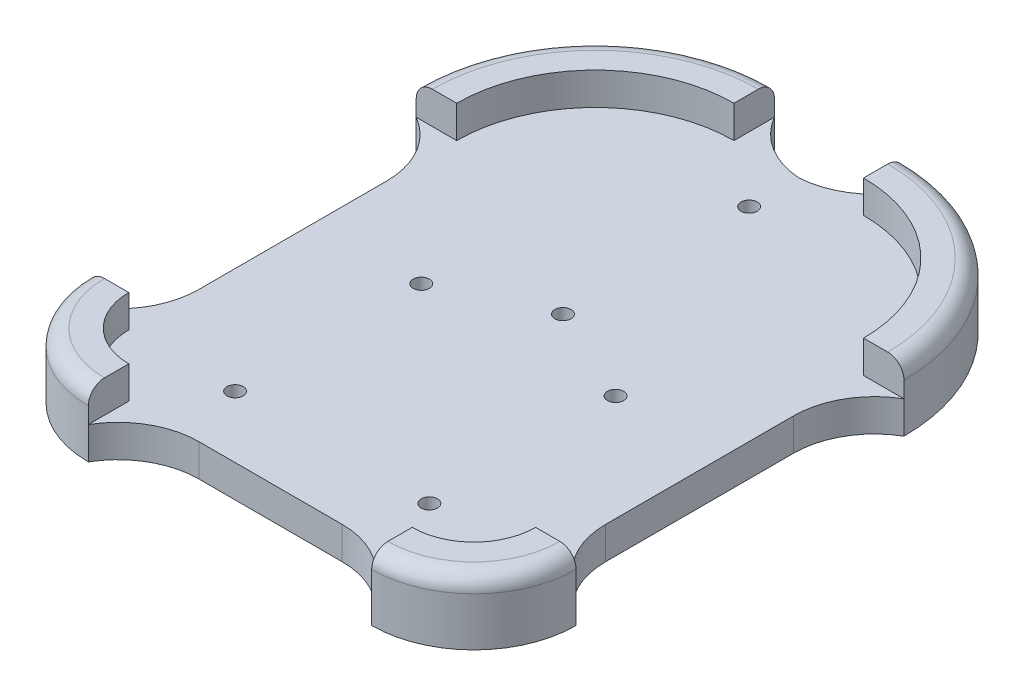
SolidWorks part; units mm, degrees
note: The reader was unsure of these and kept them because the rebuilt part matched: shared geometry of "Croquis1<3>", "Croquis3<3>".
ref_plane "Alzado" through (0, 0, 0) normal (0, 0, 1) x (1, 0, 0)
ref_plane "Planta" through (0, 0, 0) normal (0, 1, 0) x (1, 0, 0)
ref_plane "Vista lateral" through (0, 0, 0) normal (1, 0, 0) x (0, 0, -1)
sketch "Croquis1" plane through (0, 0, 0) normal (0, 1, 0) x (1, 0, 0)
  line L0 (17.5, 0) -> (-17.5, 0) construction
  line L1 (25, 7.5) -> (25, 48) construction
  line L2 (8, 65) -> (-8, 65) construction
  line L3 (0, -41.3875) -> (0, 41.3875) construction
  line L4 (-25, 7.5) -> (-25, 48) construction
  line L5 (17.5, -0.125) -> (-17.5, -0.125)
  line L6 (-25.125, 7.5) -> (-25.125, 48)
  line L7 (8, 65.125) -> (-8, 65.125)
  line L8 (25.125, 7.5) -> (25.125, 48)
  line L9 (-8, 70.125) -> (-8, 65.125)
  line L10 (-30.125, 48) -> (-25, 48)
  line L11 (-30.125, 7.5) -> (-25.125, 7.5)
  line L12 (-17.5, 0) -> (-17.5, -5.125)
  line L13 (17.5, -5.125) -> (17.5, -0.125)
  line L14 (25, 7.5) -> (30.125, 7.5)
  line L15 (8, 70.125) -> (8, 65.125)
  line L16 (30.125, 48) -> (25, 48)
  arc A0 (25, 48) -> (8, 65) centre (8, 48) ccw construction
  arc A1 (17.5, 0) -> (25, 7.5) centre (17.5, 7.5) ccw construction
  arc A2 (-17.5, 0) -> (-25, 7.5) centre (-17.5, 7.5) cw construction
  arc A3 (-25, 48) -> (-8, 65) centre (-8, 48) cw construction
  arc A4 (-17.5, -0.125) -> (-25.125, 7.5) centre (-17.5, 7.5) cw
  arc A5 (-25.125, 48) -> (-8, 65.125) centre (-8, 48) cw
  arc A6 (25.125, 48) -> (8, 65.125) centre (8, 48) ccw
  arc A7 (17.5, -0.125) -> (25.125, 7.5) centre (17.5, 7.5) ccw
  arc A8 (30.125, 48) -> (8, 70.125) centre (8, 48) ccw
  arc A9 (17.5, -5.125) -> (30.125, 7.5) centre (17.5, 7.5) ccw
  arc A10 (-30.125, 48) -> (-8, 70.125) centre (-8, 48) cw
  arc A11 (-17.5, -5.125) -> (-30.125, 7.5) centre (-17.5, 7.5) cw
  point P7 (0, 0)
  point P18 (0, 65)
  dimension "D2" = 17
  dimension "D4" = 7.5
  dimension "D1" = 8
  dimension "D3" = 40.5
  dimension "D5" = 0.125
  dimension "D6" = 5
  dimension "D7" = 5
extrude "Saliente-Extruir1" add sketch "Croquis1" along normal blind 4
extrude "Saliente-Extruir2" add sketch "Croquis1<3>" along normal blind 4 from surface at 4 contours A10 L10 A5 L9 | A11 L12 A4 L11 | L13 A9 L14 A7 | L16 A8 L15 A6 starting at face at (0, 4, -30.3709)
sketch "Croquis1<3>" plane through (0, 0, 0) normal (0, 1, 0) x (1, 0, 0) same geometry as "Croquis1"
fillet "Redondeo1" radius 10 8 edges at (8, 2, -65.125) (-8, 2, -65.125) (-17.5, 2, 0.125) (17.5, 2, 0.125) (25.125, 2, -48) (25.125, 2, -7.5) (-25.125, 2, -7.5) (-25.125, 2, -48)
fillet "Redondeo3" radius 2 4 edges at (26.4272, 8, 1.4272) (23.6447, 8, -63.6447) (-23.6447, 8, -63.6447) (-26.4272, 8, 1.4272)
sketch "Croquis3" plane through (0, 0, 0) normal (0, 1, 0) x (1, 0, 0)
  line L0 (-9.5, 10.3542) -> (-9.5, 6.1542)
  line L1 (-9.5, 27.6458) -> (-9.5, 31.8458)
  line L2 (-11.7, 34.0458) -> (-12.3, 34.0458)
  line L3 (-14.5, 27.6458) -> (-14.5, 31.8458)
  line L4 (-11.7, 3.9542) -> (-12.3, 3.9542)
  line L5 (-14.5, 10.3542) -> (-14.5, 6.1542)
  line L6 (0, -4.4) -> (0, 4.4) construction
  line L7 (14.5, 10.3542) -> (14.5, 6.1542)
  line L8 (11.7, 3.9542) -> (12.3, 3.9542)
  line L9 (14.5, 27.6458) -> (14.5, 31.8458)
  line L10 (11.7, 34.0458) -> (12.3, 34.0458)
  line L11 (9.5, 27.6458) -> (9.5, 31.8458)
  line L12 (9.5, 10.3542) -> (9.5, 6.1542)
  line L13 (2.5, 56.1458) -> (2.5, 60.3458)
  line L14 (2.5, 38.8542) -> (2.5, 34.6542)
  line L15 (0.3, 32.4542) -> (-0.3, 32.4542)
  line L22 (0.3, 62.5458) -> (-0.3, 62.5458)
  line L23 (-2.5, 56.1458) -> (-2.5, 60.3458)
  line L27 (-2.5, 38.8542) -> (-2.5, 34.6542)
  arc A0 (9.5, 10.3542) -> (9.5, 27.6458) centre (12, 19) cw
  arc A1 (-14.5, 27.6458) -> (-14.5, 10.3542) centre (-12, 19) ccw
  circle A2 centre (-12, 30.5) radius 1
  arc A3 (-9.5, 31.8458) -> (-11.7, 34.0458) centre (-11.7, 31.8458) ccw
  arc A4 (-12.3, 34.0458) -> (-14.5, 31.8458) centre (-12.3, 31.8458) ccw
  arc A5 (12.3, 3.9542) -> (14.5, 6.1542) centre (12.3, 6.1542) ccw
  circle A6 centre (-12, 7.5) radius 1
  arc A7 (-9.5, 6.1542) -> (-11.7, 3.9542) centre (-11.7, 6.1542) cw
  arc A8 (-12.3, 3.9542) -> (-14.5, 6.1542) centre (-12.3, 6.1542) cw
  arc A9 (-9.5, 10.3542) -> (-9.5, 27.6458) centre (-12, 19) ccw
  arc A10 (9.5, 6.1542) -> (11.7, 3.9542) centre (11.7, 6.1542) ccw
  circle A11 centre (12, 7.5) radius 1
  arc A12 (12.3, 34.0458) -> (14.5, 31.8458) centre (12.3, 31.8458) cw
  arc A13 (9.5, 31.8458) -> (11.7, 34.0458) centre (11.7, 31.8458) cw
  circle A14 centre (12, 30.5) radius 1
  arc A15 (14.5, 27.6458) -> (14.5, 10.3542) centre (12, 19) cw
  circle A24 centre (0, 47.5) radius 9
  circle A25 centre (0, 59) radius 1
  arc A26 (2.5, 60.3458) -> (0.3, 62.5458) centre (0.3, 60.3458) ccw
  arc A27 (-0.3, 62.5458) -> (-2.5, 60.3458) centre (-0.3, 60.3458) ccw
  circle A31 centre (0, 36) radius 1
  arc A32 (2.5, 34.6542) -> (0.3, 32.4542) centre (0.3, 34.6542) cw
  arc A33 (-0.3, 32.4542) -> (-2.5, 34.6542) centre (-0.3, 34.6542) cw
  point P1 (-12, 3.9542)
  point P14 (-12, 34.0458)
  point P51 (0, 62.5458)
  point P60 (-0.7004, 60.4859)
  point P61 (0, 0)
  point P62 (0, 0)
  point P63 (0, 0)
  point P64 (0, 0)
  point P65 (0, 0)
  point P66 (0, 0)
  point P67 (0, 0)
  point P68 (0, 37.2261)
  point P73 (0, 0)
  point P76 (0, 0)
  point P77 (0, 0)
  point P78 (0, 0)
  point P79 (0, 32.4542)
  dimension "D3" = 2
  dimension "D4" = 2.2
  dimension "D6" = 9
  dimension "D12" = 2.2
  dimension "D1" = 5
  dimension "D2" = 11.5
  dimension "D5" = 11.5
  dimension "D7" = 6.4
  dimension "D8" = 12
  dimension "D9" = 19
  dimension "D10" = 5
  dimension "D11" = 11.5
  dimension "D13" = 6.4
  dimension "D14" = 47.5
  dimension "D15" = 11.5
extrude "Cortar-Extruir1" cut sketch "Croquis3" along normal blind 2 contours A9 L0 A7 L4 A8 L5 A1 L3 A4 L2 A3 L1 A6 A2 | L9 A15 L7 A5 L8 A10 L12 A0 L11 A13 L10 A12 A11 A14 | A24 | L15 A33 L27 A24 L14 A32 A31 | A27 L22 A26 L13 A24 L23 A25
extrude "Cortar-Extruir2" cut sketch "Croquis3<3>" along normal through all contours A6 | A2 | A11 | A14 | A25 | A31
sketch "Croquis3<3>" plane through (0, 0, 0) normal (0, 1, 0) x (1, 0, 0) same geometry as "Croquis3"
